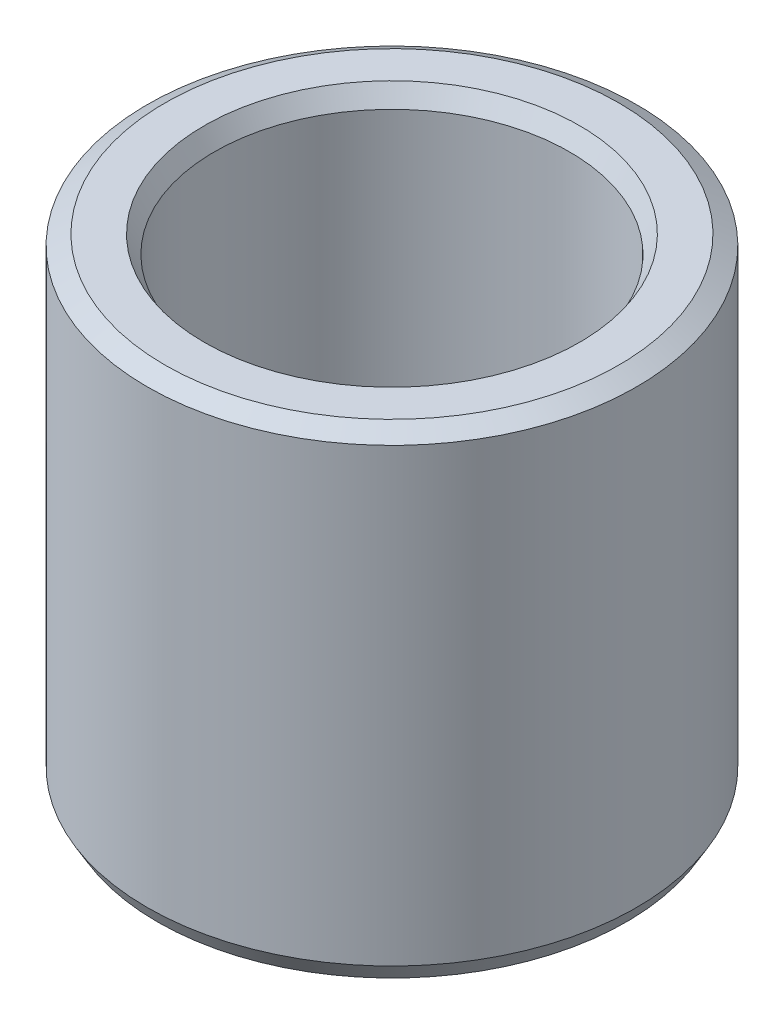
SolidWorks part; units mm, degrees
ref_plane "Front Plane" through (0, 0, 0) normal (0, 0, 1) x (1, 0, 0)
ref_plane "Top Plane" through (0, 0, 0) normal (0, 1, 0) x (1, 0, 0)
ref_plane "Right Plane" through (0, 0, 0) normal (1, 0, 0) x (0, 0, -1)
sketch "Sketch1" plane through (0, 0, 0) normal (0, 1, 0) x (1, 0, 0)
  circle A0 centre (0, 0) radius 37.5
  dimension "SLEEVE_OD" = 75
extrude "Boss-Extrude1" add sketch "Sketch1" along normal blind 73.3779
sketch "Sketch2" plane through (0, 0, 0) normal (0, 1, 0) x (1, 0, 0)
  circle A0 centre (0, 0) radius 27.2228
  dimension "BORE_D" = 54.4455
extrude "Cut-Extrude1" cut sketch "Sketch2" along normal through all
chamfer "Chamfer1" distance 1.5553 angle 60 4 edges at (0, 73.3779, 27.2228) (0, 0, 27.2228) (0, 0, 37.5) (0, 73.3779, 37.5) first distance on face at (0, 73.3779, 27.2228) first distance on face at (0, 0, 27.2228) first distance on face at (0, 73.3779, 37.5)
